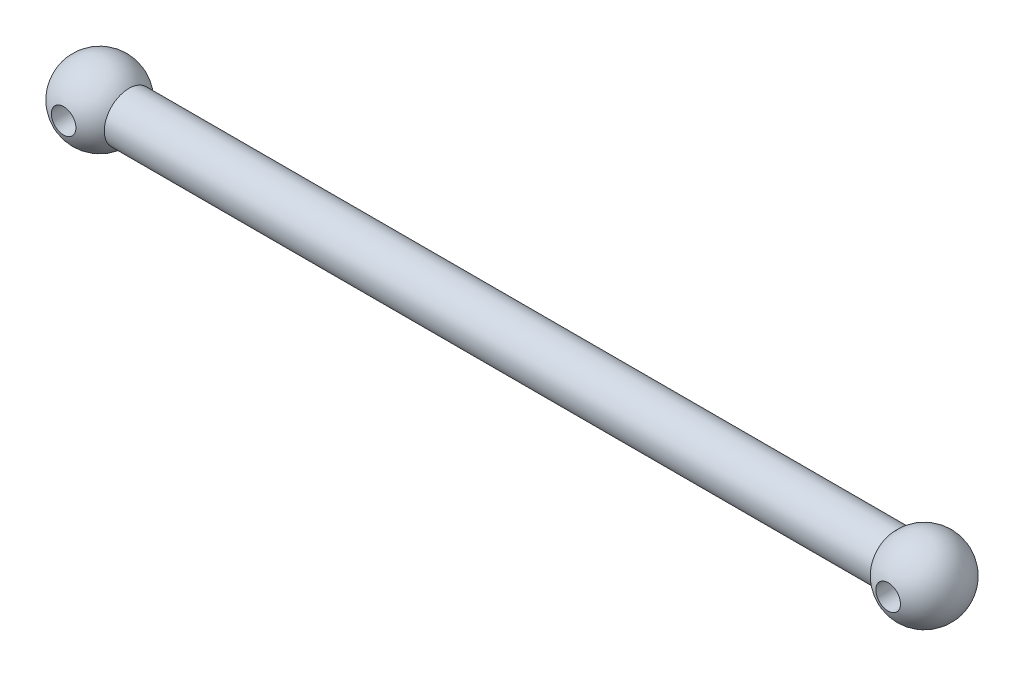
SolidWorks part; units mm, degrees
ref_plane "Front Plane" through (0, 0, 0) normal (0, 0, 1) x (1, 0, 0)
ref_plane "Top Plane" through (0, 0, 0) normal (0, 1, 0) x (1, 0, 0)
ref_plane "Right Plane" through (0, 0, 0) normal (1, 0, 0) x (0, 0, -1)
sketch "Sketch1" plane through (0, 0, 0) normal (0, 1, 0) x (1, 0, 0)
  line L0 (-31.1315, 2) -> (31.1315, 2)
  line L1 (-33.5, 0) -> (33.5, 0) construction
  line L2 (-31.1315, -2) -> (31.1315, -2)
  line L3 (-30.4, 0) -> (-36.6, 0)
  line L4 (30.4, 0) -> (36.6, 0)
  circle A0 centre (-33.5, 0) radius 3.1
  circle A1 centre (33.5, 0) radius 3.1
  point P13 (0, 0)
  dimension "D1" = 6.2
  dimension "D2" = 2
  dimension "D3" = 2
  dimension "D4" = 67
revolve "Revolve2" add sketch "Sketch1" angle 360 about L1 region at (-33.5, 0, 1.3157) region at (0, 0, 1.0039) region at (33.5, 0, 1.3157)
sketch "Sketch2" plane through (0, 0, 0) normal (0, 0, 1) x (1, 0, 0)
  line L0 (0, -3.41) -> (0, 3.41) construction
  circle A2 centre (33.5, 0) radius 1
  circle A3 centre (-33.5, 0) radius 1
  dimension "D1" = 2
  dimension "D2" = 33.5
extrude "Cut-Extrude1" cut sketch "Sketch2" against normal through all both and the other way through all
